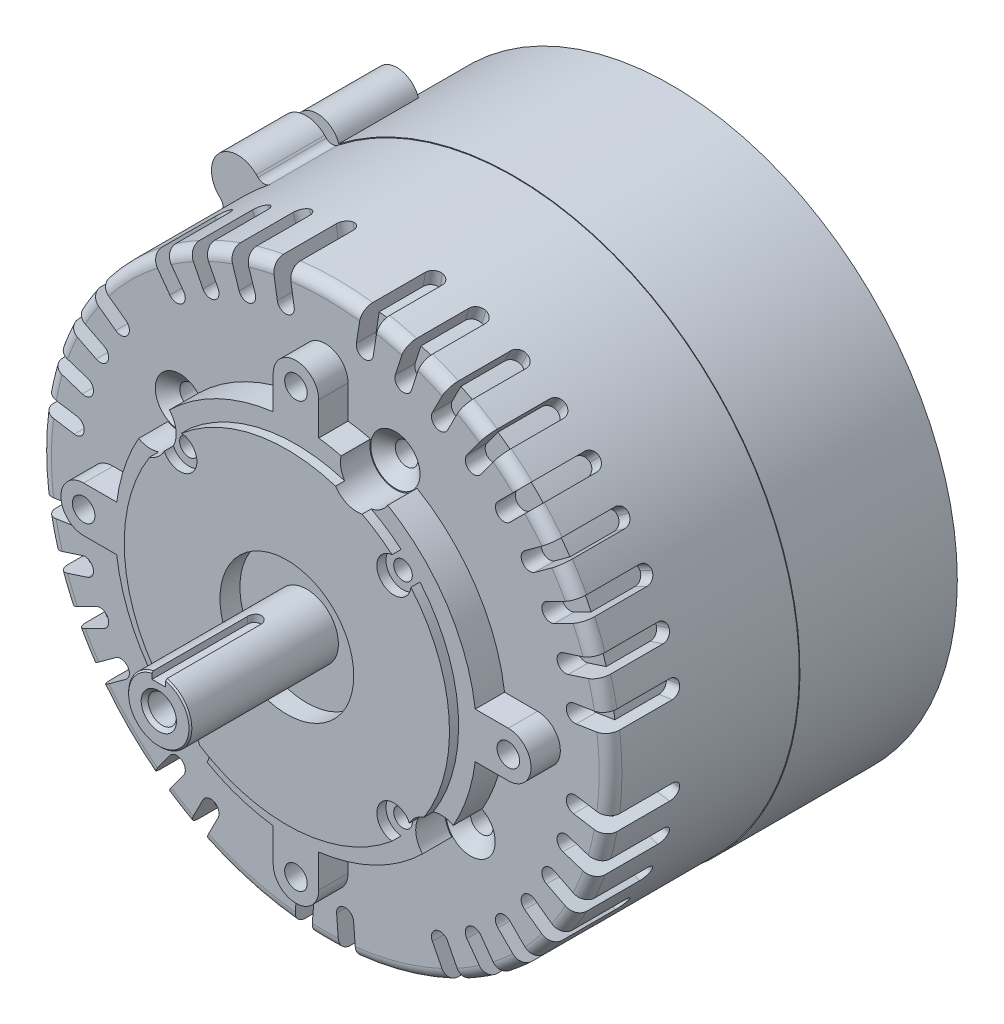
SolidWorks part; units mm, degrees
material "Cast Alloy Steel"
ref_plane "Front Plane" through (0, 0, 0) normal (0, 0, 1) x (1, 0, 0)
ref_plane "Top Plane" through (0, 0, 0) normal (0, 1, 0) x (1, 0, 0)
ref_plane "Right Plane" through (0, 0, 0) normal (1, 0, 0) x (0, 0, -1)
sketch "Sketch72" plane through (0, 0, 0) normal (0, 0, 1) x (1, 0, 0)
  circle A0 centre (0, 0) radius 100.5
  dimension "D1" = 201
extrude "Boss-Extrude34" add sketch "Sketch72" along normal blind 121.6 from offset 13.6 separate body
sketch "Sketch74" plane through (0, 0, 135.2) normal (0, 0, 1) x (1, 0, 0)
  circle A2 centre (0, 0) radius 100.25
  circle A3 centre (0, 0) radius 100.25
  dimension "D1" = 0.25
extrude "Cut-Extrude33" cut sketch "Sketch74" against normal blind 66.3 flip side to cut
sketch "Sketch73" plane through (0, 0, 0) normal (0, 0, 1) x (1, 0, 0)
  line L0 (-73.0441, 73.0441) -> (0, 0) construction
  line L1 (0, 0) -> (-43.4732, 0) construction
  line L2 (-66.5034, 79.5849) -> (-59.9627, 73.0441)
  line L3 (-59.9627, 73.0441) -> (-73.0441, 59.9627)
  line L4 (-73.0441, 59.9627) -> (-79.5849, 66.5034)
  circle A0 centre (-73.0441, 73.0441) radius 9.25
  dimension "D1" = 18.5
  dimension "D2" = 45
  dimension "D3" = 103.3
extrude "Boss-Extrude35" add sketch "Sketch73" along normal blind 24 from surface contours A0 | A0 L4 L3 | A0 L3 L2 region at (-62.8846, 73.0441, 0) region at (-73.0441, 73.0441, 0) region at (-73.0441, 62.8846, 0) starting at face at (100.25, 0, 68.9)
sketch "Sketch76" plane through (0, 0, 0) normal (0, 0, 1) x (1, 0, 0)
  line L0 (0, 52.4) -> (0, 74.6) construction
  line L1 (-8, 52.4) -> (-8, 74.6)
  line L2 (8, 52.4) -> (8, 74.6)
  line L3 (52.4, -8) -> (74.6, -8)
  line L4 (52.4, 8) -> (74.6, 8)
  line L5 (52.4, 0) -> (74.6, 0) construction
  line L6 (-8, -52.4) -> (-8, -74.6)
  line L7 (8, -52.4) -> (8, -74.6)
  line L8 (0, -52.4) -> (0, -74.6) construction
  line L9 (-52.4, 8) -> (-74.6, 8)
  line L10 (-52.4, -8) -> (-74.6, -8)
  line L11 (-52.4, 0) -> (-74.6, 0) construction
  line L12 (0, 0) -> (0, 52.4) construction
  line L13 (-51.0721, 39.189) -> (0, 0) construction
  line L14 (0, 0) -> (24.6352, 59.4747) construction
  line L15 (0, 0) -> (-39.189, -51.0721) construction
  circle A0 centre (0, 0) radius 63.5
  arc A1 (-8, 52.4) -> (8, 52.4) centre (0, 52.4) ccw
  arc A2 (8, 74.6) -> (-8, 74.6) centre (0, 74.6) ccw
  circle A3 centre (0, 0) radius 74.6 construction
  arc A4 (52.4, 8) -> (52.4, -8) centre (52.4, 0) ccw
  arc A5 (74.6, -8) -> (74.6, 8) centre (74.6, 0) ccw
  arc A6 (8, -52.4) -> (-8, -52.4) centre (0, -52.4) ccw
  arc A7 (-8, -74.6) -> (8, -74.6) centre (0, -74.6) ccw
  arc A8 (-52.4, -8) -> (-52.4, 8) centre (-52.4, 0) ccw
  arc A9 (-74.6, 8) -> (-74.6, -8) centre (-74.6, 0) ccw
  circle A10 centre (-51.0721, 39.189) radius 9
  circle A11 centre (0, 0) radius 64.375 construction
  circle A12 centre (-39.189, -51.0721) radius 9
  circle A13 centre (51.0721, -39.189) radius 9
  circle A14 centre (24.6352, 59.4747) radius 9
  point P5 (0, 63.5)
  point P15 (63.5, 0)
  point P22 (0, -63.5)
  point P29 (-63.5, 0)
  dimension "D1" = 127
  dimension "D2" = 149.2
  dimension "D3" = 8
  dimension "D5" = 128.75
  dimension "D6" = 18
  dimension "D7" = 52.5
  dimension "D8" = 22.5
  dimension "D9" = 142.5
  dimension "D4" = 4
extrude "Boss-Extrude36" add sketch "Sketch76" along normal blind 10.3 from surface contours L9 A9 L10 A0 | A8 L10 A0 L6 A6 L7 L3 A4 L4 L2 A1 L1 L9 | L2 A2 L1 A0 | L3 A5 L4 A0 | L6 A7 L7 A0 | L10 A8 L9 A0 | L1 A1 L2 A0 | L4 A4 L3 A0 | L7 A6 L6 A0 region at (0.1312, -0.0758, 0) region at (0, 54.6323, 0) region at (0, 72.1976, 0) region at (-72.1976, 0, 0) region at (-54.6323, 0, 0) region at (54.6323, 0, 0) region at (72.1976, 0, 0) region at (0, -72.1976, 0) region at (0, -54.6323, 0) starting at face at (100.25, 0, 135.2)
sketch "Sketch78" plane through (0, 0, 0) normal (0, 0, 1) x (1, 0, 0)
  line L0 (-69.1197, 76.8979) -> (-76.8979, 69.1197) construction
  line L1 (-63.4628, 71.241) -> (-71.241, 63.4628)
  line L2 (-74.7765, 82.5547) -> (-82.5547, 74.7765)
  line L3 (-73.0441, 73.0441) -> (0, 0) construction
  arc A1 (-63.4628, 71.241) -> (-74.7765, 82.5547) centre (-69.1197, 76.8979) ccw
  arc A2 (-82.5547, 74.7765) -> (-71.241, 63.4628) centre (-76.8979, 69.1197) ccw
  circle A3 centre (0, 0) radius 103.25 construction
  point P2 (-73.0088, 73.0088)
  dimension "D1" = 206.5
  dimension "D2" = 8
  dimension "D3" = 11
extrude "Boss-Extrude37" add sketch "Sketch78" against normal blind 28 from surface contours A1 L2 A2 L1 starting at face at (-73.614, 73.614, 68.9)
sketch "Sketch79" plane through (0, 0, 0) normal (0, 0, 1) x (1, 0, 0)
  line L0 (0, 0) -> (37.6181, 37.6181) construction
  line L1 (0, 0) -> (44.0536, 0) construction
  line L2 (0, 0) -> (37.6181, 37.6181) construction
  circle A0 centre (0, 0) radius 57.15
  circle A1 centre (0, 0) radius 53.2 construction
  circle A2 centre (37.6181, 37.6181) radius 6
  circle A3 centre (37.6181, -37.6181) radius 6
  circle A4 centre (-37.6181, -37.6181) radius 6
  circle A5 centre (-37.6181, 37.6181) radius 6
  dimension "D1" = 114.3
  dimension "D2" = 106.4
  dimension "D4" = 12
  dimension "D3" = 45
  dimension "D6" = 53.2
  dimension "D5" = 4
extrude "Boss-Extrude38" add sketch "Sketch79" along normal blind 3.2 from surface contours A5 A0 A4 A3 A2 region at (0, 0, 0) starting at face at (-1.0275, 0.6893, 145.5)
extrude "Cut-Extrude34" cut sketch "Sketch76<3>" along normal through all from surface contours A0 A10 | A0 A14 | A0 A13 | A0 A12 region at (-47.5743, 36.5051, 0) region at (22.9481, 55.4015, 0) region at (-36.5051, -47.5743, 0) region at (47.5743, -36.5051, 0) starting at face at (100.25, 0, 135.2)
sketch "Sketch76<3>" plane through (0, 0, 0) normal (0, 0, 1) x (1, 0, 0) same geometry as "Sketch76"
sketch "Sketch80" plane through (0, 0, 0) normal (0, 0, 1) x (1, 0, 0)
  circle A0 centre (0, 0) radius 23.5
  dimension "D1" = 47
extrude "Cut-Extrude35" cut sketch "Sketch80" against normal blind 7 from surface starting at face at (0.9681, 4.0766, 148.7)
sketch "Sketch75" plane through (0, 0, 0) normal (0, 0, 1) x (1, 0, 0)
  circle A0 centre (0, 0) radius 11.115
  dimension "D1" = 22.23
extrude "Boss-Extrude39" add sketch "Sketch75" along normal offset from surface (52 mm away) 45 from surface contours A0 region at (0, 0, 0) up to face at (23.5, 0, 148.7) offset beyond the face yes starting at face at (23.5, 0, 141.7)
sketch "Sketch81" plane through (0, 0, 0) normal (0, 0, 1) x (1, 0, 0)
  line L1 (-2.39, 8.465) -> (2.39, 8.465)
  line L2 (-2.39, 8.465) -> (-2.39, 13.765)
  line L3 (-2.39, 13.765) -> (2.39, 13.765)
  line L4 (2.39, 8.465) -> (2.39, 13.765)
  line L5 (-2.39, 8.465) -> (2.39, 13.765) construction
  line L6 (-2.39, 13.765) -> (2.39, 8.465) construction
  circle A0 centre (0, 0) radius 11.115 construction
  circle A1 centre (0, 0) radius 11.115 construction
  point P0 (0, 11.115)
  dimension "D1" = 19.58
  dimension "D2" = 4.78
extrude "Cut-Extrude36" cut sketch "Sketch81" against normal blind 36 from surface starting at face at (11.115, 0, 193.7)
fillet "Fillet10" radius 4 1 edges at (100.25, 0, 135.2)
chamfer "Chamfer4" distance 0.5 angle 45 1 edges at (0, -11.115, 193.7)
sketch "Sketch82" plane through (0, 0, 0) normal (0, 0, 1) x (1, 0, 0)
  line L0 (-52.1953, 71.8407) -> (-65.6556, 90.3672) construction
  line L1 (-54.6224, 70.0774) -> (-68.0827, 88.6038)
  line L2 (-49.7683, 73.6041) -> (-63.2286, 92.1306)
  line L3 (0, 0) -> (-37.3757, 0) construction
  arc A0 (-77.1258, 64.0443) -> (-64.0443, 77.1258) centre (0, 0) ccw construction
  arc A1 (-54.6224, 70.0774) -> (-49.7683, 73.6041) centre (-52.1953, 71.8407) ccw
  arc A2 (-63.2286, 92.1306) -> (-68.0827, 88.6038) centre (-65.6556, 90.3672) ccw
  point P5 (-58.9255, 81.104)
  dimension "D1" = 54
  dimension "D2" = 6
  dimension "D3" = 22.9
extrude "Cut-Extrude37" cut sketch "Sketch82" against normal blind 25.482 from surface starting at face at (96.25, 0, 135.2)
fillet "Fillet6" radius 3 3 edges at (-57.9743, 74.6908, 109.718) (-50.432, 69.4137, 109.718) (-53.1202, 78.2175, 109.718)
pattern_circular "CirPattern1" count 40 over 360 about axis through (0, 0, 68.9) along (0, 0, 1) skipping 4, 14, 22, 23, 24, 25, 26, 27, 28, 29, 34, 39 of "Fillet6", "Cut-Extrude37" reverse direction yes
fillet "Fillet7" 2 edges at (-2.39, 9.66, 157.7) (2.39, 9.66, 157.7) type full round first side face at (-2.39, 9.8477, 179.15) second side face at (2.39, 9.7452, 179.25) middle face at (0, 9.725, 157.7)
sketch "Sketch84" plane through (0, 0, 0) normal (0, 0, 1) x (1, 0, 0)
  line L0 (8.7639, -111.3557) -> (6.9672, -88.5263) construction
  line L3 (5.7731, -111.591) -> (3.9764, -88.7616)
  line L4 (11.7546, -111.1203) -> (9.9579, -88.2909)
  line L5 (0, 0) -> (0, -77.8847) construction
  line L6 (-8.7639, -111.3557) -> (-6.9672, -88.5263) construction
  line L7 (-5.7731, -111.591) -> (-3.9764, -88.7616)
  line L8 (-11.7546, -111.1203) -> (-9.9579, -88.2909)
  line L9 (-50.7107, -99.5254) -> (-40.3144, -79.1214) construction
  line L10 (-53.3838, -98.1635) -> (-42.9874, -77.7594)
  line L11 (-48.0377, -100.8874) -> (-37.6413, -80.4834)
  line L12 (-65.6556, -90.3672) -> (-52.1953, -71.8407) construction
  line L13 (-63.2286, -92.1306) -> (-49.7683, -73.6041)
  line L14 (-68.0827, -88.6038) -> (-54.6224, -70.0774)
  line L15 (0, 0) -> (-8.7639, -111.3557) construction
  line L16 (0, 0) -> (-65.6556, -90.3672) construction
  arc A2 (5.7731, -111.591) -> (11.7546, -111.1203) centre (8.7639, -111.3557) ccw
  arc A3 (9.9579, -88.2909) -> (3.9764, -88.7616) centre (6.9672, -88.5263) ccw
  arc A4 (79.3043, 61.3261) -> (-72.977, 68.7344) centre (0, 0) ccw construction
  arc A6 (-5.7731, -111.591) -> (-11.7546, -111.1203) centre (-8.7639, -111.3557) cw
  arc A7 (-9.9579, -88.2909) -> (-3.9764, -88.7616) centre (-6.9672, -88.5263) cw
  arc A8 (-53.3838, -98.1635) -> (-48.0377, -100.8874) centre (-50.7107, -99.5254) ccw
  arc A9 (-37.6413, -80.4834) -> (-42.9874, -77.7594) centre (-40.3144, -79.1214) ccw
  arc A10 (-63.2286, -92.1306) -> (-68.0827, -88.6038) centre (-65.6556, -90.3672) cw
  arc A11 (-54.6224, -70.0774) -> (-49.7683, -73.6041) centre (-52.1953, -71.8407) cw
  point P2 (7.8655, -99.941)
  point P15 (-7.8655, -99.941)
  point P25 (-45.5125, -89.3234)
  point P32 (-58.9255, -81.104)
  dimension "D1" = 6
  dimension "D2" = 4.5
  dimension "D3" = 22.9
  dimension "D5" = 31.5
  dimension "D4" = 2
extrude "Cut-Extrude38" cut sketch "Sketch84" against normal blind 25.482 from surface starting at face at (-1.0275, 0.6893, 135.2)
fillet "Fillet8" radius 3 12 edges at (10.4053, -93.9759, 109.718) (6.7318, -85.5355, 109.718) (-4.4238, -94.4466, 109.718) (-6.7318, -85.5355, 109.718) (-40.2302, -85.5644, 109.718) (-38.9524, -76.4484, 109.718) (-53.1202, -78.2175, 109.718) (-50.432, -69.4137, 109.718) (4.4238, -94.4466, 109.718) (-10.4053, -93.9759, 109.718) (-45.5763, -82.8404, 109.718) (-57.9743, -74.6908, 109.718)
sketch "Sketch83" plane through (0, 0, 0) normal (0, 0, 1) x (1, 0, 0)
  circle A0 centre (0, 0) radius 95.5
  dimension "D1" = 191
extrude "Boss-Extrude40" add sketch "Sketch83" along normal offset from surface (59.3 mm away) 7 from surface up to face at (-1.0275, 0.6893, 135.2) starting at face at (-46.3547, 46.3547, 68.9)
sketch "Sketch85" plane through (0, 0, 145.5) normal (0, 0, 1) x (1, 0, 0)
  point P0 (-37.6181, 37.6181)
  point P3 (37.6181, 37.6181)
  point P6 (37.6181, -37.6181)
  point P9 (-37.6181, -37.6181)
hole_wizard "5/16-18 Tapped Hole1" positions "Sketch85" profile "Sketch86" tap size "5/16-18" standard "ANSI Inch"
sketch "Sketch86" plane through (-37.6181, 37.6181, 145.5) normal (1, 0, 0) x (0, -1, 0)
  line L0 (0, 0) -> (0, 16.9611)
  line L1 (0, 16.9611) -> (3.2639, 15)
  line L2 (3.2639, 15) -> (3.2639, 0)
  line L5 (3.2639, 0) -> (0, 0)
  line L10 (0, 16.9611) -> (-3.2639, 15) construction
  line L11 (0, -6.35) -> (0, 107.95) construction
  dimension "Tap Drill Dia." = 6.5278
  dimension "Tap Drill Depth" = 15
  dimension "Drill Angle" = 118
cosmetic thread "Hole Thread1" parameters "D1"=15.88, "D2"=7.9375
cosmetic thread "Hole Thread2" parameters "D1"=15.88, "D2"=7.9375
cosmetic thread "Hole Thread3" parameters "D1"=15.88, "D2"=7.9375
cosmetic thread "Hole Thread4" parameters "D1"=15.88, "D2"=7.9375
sketch "Sketch87" plane through (0, 0, 145.5) normal (0, 0, 1) x (1, 0, 0)
  point P0 (-74.6, 0)
  point P3 (0, 74.6)
  point P6 (74.6, 0)
  point P9 (0, -74.6)
hole_wizard "3/8-16 Tapped Hole2" positions "Sketch87" profile "Sketch88" tap size "3/8-16" standard "ANSI Inch"
sketch "Sketch88" plane through (-74.6, 0, 145.5) normal (1, 0, 0) x (0, -1, 0)
  line L0 (0, 0) -> (0, 20.3847)
  line L1 (0, 20.3847) -> (3.9687, 18)
  line L2 (3.9687, 18) -> (3.9687, 0)
  line L5 (3.9687, 0) -> (0, 0)
  line L10 (0, 20.3847) -> (-3.9688, 18) construction
  line L11 (0, -6.35) -> (0, 107.95) construction
  dimension "Tap Drill Dia." = 7.9375
  dimension "Tap Drill Depth" = 18
  dimension "Drill Angle" = 118
cosmetic thread "Hole Thread5" parameters "D1"=19.05, "D2"=9.525
cosmetic thread "Hole Thread6" parameters "D1"=19.05, "D2"=9.525
cosmetic thread "Hole Thread7" parameters "D1"=19.05, "D2"=9.525
cosmetic thread "Hole Thread8" parameters "D1"=19.05, "D2"=9.525
hole_wizard "5/16 (0.3125) Diameter Hole3" positions "3DSketch6" profile "Sketch89" hole size "5/16" standard "ANSI Inch"
sketch3d "3DSketch6"
  line L0 (-39.189, -51.0721, 145.5) -> (-39.189, -51.0721, 135.2) construction
  line L1 (51.0721, -39.189, 145.5) -> (51.0721, -39.189, 135.2) construction
  line L2 (24.6352, 59.4747, 145.5) -> (24.6352, 59.4747, 135.2) construction
  line L3 (-51.0721, 39.189, 145.5) -> (-51.0721, 39.189, 135.2) construction
  point P0 (-39.189, -51.0721, 135.2)
  point P4 (51.0721, -39.189, 135.2)
  point P8 (24.6352, 59.4747, 135.2)
  point P12 (-51.0721, 39.189, 135.2)
sketch "Sketch89" plane through (-39.189, -51.0721, 135.2) normal (1, 0, 0) x (0, -1, 0)
  line L0 (0, 0) -> (0, 25.3147)
  line L1 (0, 25.3147) -> (3.9687, 22.93)
  line L2 (3.9687, 22.93) -> (3.9687, 3.928)
  line L3 (3.9687, 3.928) -> (8.65, 0)
  line L5 (8.65, 0) -> (0, 0)
  line L6 (-3.9687, 3.928) -> (-8.65, 0) construction
  line L10 (0, 25.3147) -> (-3.9688, 22.93) construction
  line L11 (0, -6.35) -> (0, 107.95) construction
  dimension "Hole Dia." = 7.9375
  dimension "Hole Depth" = 22.93
  dimension "Near C'Sink Dia." = 17.3
  dimension "Near C'Sink Angle" = 100
  dimension "Drill Angle" = 118
sketch "Sketch90" plane through (0, 0, 193.7) normal (0, 0, 1) x (1, 0, 0)
  point P0 (0, 0)
hole_wizard "7/16-20 Tapped Hole1" positions "Sketch90" profile "Sketch92" tap size "7/16-20" standard "ANSI Inch"
sketch "Sketch92" plane through (0, 0, 193.7) normal (1, 0, 0) x (0, -1, 0)
  line L0 (0, 0) -> (0, 37.9806)
  line L1 (0, 37.9806) -> (4.9606, 35)
  line L2 (4.9606, 35) -> (4.9606, 1.2306)
  line L3 (4.9606, 1.2306) -> (6.1913, 0)
  line L5 (6.1913, 0) -> (0, 0)
  line L6 (-4.9606, 1.2306) -> (-6.1913, 0) construction
  line L10 (0, 37.9806) -> (-4.9606, 35) construction
  line L11 (0, -6.35) -> (0, 107.95) construction
  dimension "Tap Drill Dia." = 9.9212
  dimension "Tap Drill Depth" = 35
  dimension "Near C'Sink Dia." = 12.3825
  dimension "Near C'Sink Angle" = 90
  dimension "Drill Angle" = 118
cosmetic thread "Hole Thread13" parameters "D1"=30, "D2"=11.1125
fillet "Fillet9" radius 3 2 edges at (-64.0443, 77.1258, 80.9) (-77.1258, 64.0443, 80.9)
